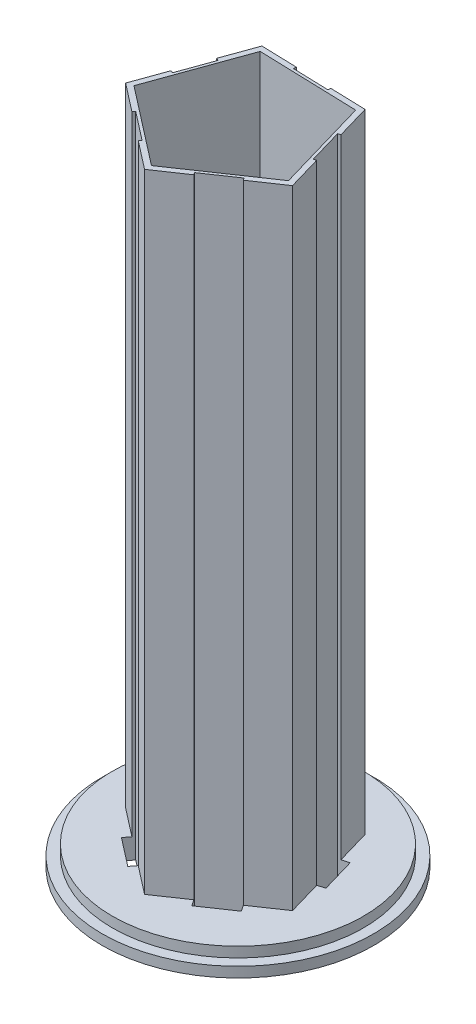
SolidWorks part; units mm, degrees
ref_plane "Front Plane" through (0, 0, 0) normal (0, 0, 1) x (1, 0, 0)
ref_plane "Top Plane" through (0, 0, 0) normal (0, 1, 0) x (1, 0, 0)
ref_plane "Right Plane" through (0, 0, 0) normal (1, 0, 0) x (0, 0, -1)
sketch "Sketch1" plane through (0, 0, 0) normal (0, 1, 0) x (1, 0, 0)
  circle A0 centre (0, 0) radius 40
  dimension "D1" = 80
extrude "Boss-Extrude1" add sketch "Sketch1" along normal blind 6
sketch "Sketch2" plane through (0, 6, 0) normal (0, 1, 0) x (1, 0, 0)
  line L0 (16.3609, 21.0989) -> (-15.0104, 22.08)
  line L1 (23.2611, -8.3705) -> (15.1489, 19.536)
  line L2 (15.1489, 19.536) -> (-13.8986, 20.4445)
  line L3 (-13.8986, 20.4445) -> (-23.7387, -6.9006)
  line L4 (-23.7387, -6.9006) -> (-0.7728, -24.7093)
  line L5 (-0.7728, -24.7093) -> (23.2611, -8.3705)
  line L6 (-15.0104, 22.08) -> (-25.6378, -7.4527)
  line L7 (-25.6378, -7.4527) -> (-0.8346, -26.686)
  line L8 (-0.8346, -26.686) -> (25.122, -9.0402)
  line L9 (25.122, -9.0402) -> (16.3609, 21.0989)
  circle A0 centre (0, 0) radius 20 construction
  dimension "D1" = 40
  dimension "D2" = 1.6
extrude "Boss-Extrude2" add sketch "Sketch2" along normal blind 185
sketch "Sketch3" plane through (0.6752, 0, -21.5894) normal (0.0313, 0, -0.9995) x (-0.9995, 0, -0.0313)
  line L0 (-15.6933, 6) -> (15.6933, 6) construction
  line L1 (-5.25, 191) -> (5.25, 191)
  line L2 (-5.25, 191) -> (-5.25, 6)
  line L3 (-5.25, 6) -> (5.25, 6)
  line L4 (5.25, 191) -> (5.25, 6)
  line L5 (-5.25, 191) -> (5.25, 6) construction
  line L6 (-5.25, 6) -> (5.25, 191) construction
  line L7 (-15.6933, 191) -> (15.6933, 191) construction
  point P0 (0, 98.5)
  point P7 (0, 6)
  point P10 (0, 0)
  dimension "D1" = 10.5
extrude "Cut-Extrude1" cut sketch "Sketch3" against normal blind 0.8
pattern_circular "CirPattern1" count 5 over 360 about axis through (0, 6, 0) along (0, -1, 0) of "Cut-Extrude1"
sketch "Sketch4" plane through (0, 6, 0) normal (0, 1, 0) x (1, 0, 0)
  line L0 (-17.7938, 11.9827) -> (-21.349, 2.1029)
  line L1 (-17.7938, 11.9827) -> (-20.6166, 12.9985)
  line L2 (-21.349, 2.1029) -> (-24.1718, 3.1187)
  line L3 (-20.6166, 12.9985) -> (-24.1718, 3.1187)
  dimension "D1" = 3
extrude "Cut-Extrude2" cut sketch "Sketch4" against normal up to surface (6 mm away) up to face at (0, 0, 40)
pattern_circular "CirPattern2" count 5 over 360 about axis through (0, 6, 0) along (0, -1, 0) of "Cut-Extrude2"
sketch "Sketch5" plane through (0, 6, 0) normal (0, 1, 0) x (1, 0, 0)
  circle A0 centre (0, 0) radius 40 construction
  circle A1 centre (0, 0) radius 40
  circle A2 centre (0, 0) radius 37
  dimension "D1" = 3
extrude "Cut-Extrude3" cut sketch "Sketch5" against normal offset from surface (3 mm away) 3 up to face at (0.6971, 0, -22.2891)
